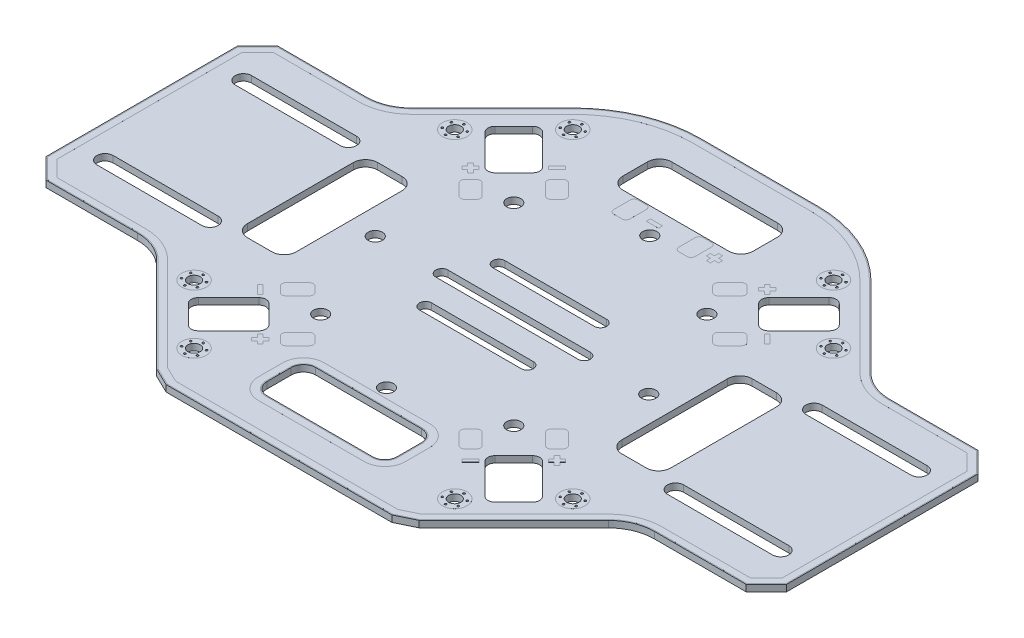
SolidWorks part; units mm, degrees
material "PLA"
ref_plane "Front Plane" through (0, 0, 0) normal (0, 0, 1) x (1, 0, 0)
ref_plane "Top Plane" through (0, 0, 0) normal (0, 1, 0) x (1, 0, 0)
ref_plane "Right Plane" through (0, 0, 0) normal (1, 0, 0) x (0, 0, -1)
sketch "Sketch1" plane through (0, 0, 0) normal (0, 1, 0) x (1, 0, 0)
  line L0 (0, 60.3186) -> (0, -57.6814) construction
  line L1 (-27.75, -57.6814) -> (27.75, -57.6814)
  line L2 (-13, -47.6814) -> (13, -47.6814)
  line L3 (-16, -38.6814) -> (-16, -44.6814)
  line L4 (16, -38.6814) -> (16, -44.6814)
  line L5 (-16, -41.6814) -> (16, -41.6814) construction
  line L6 (-13, -35.6814) -> (13, -35.6814)
  line L7 (-27.75, -57.6814) -> (-32.25, -55.502)
  line L8 (27.75, -57.6814) -> (32.25, -55.502)
  line L9 (-32.25, -55.502) -> (32.25, -55.502) construction
  line L10 (32.25, -55.502) -> (55.502, -32.25)
  line L11 (-32.25, -55.502) -> (-55.502, -32.25)
  line L12 (-43.876, 43.876) -> (43.876, -43.876) construction
  line L13 (-43.876, -43.876) -> (43.876, 43.876) construction
  line L14 (37.6888, -42.285) -> (42.285, -37.6888)
  line L15 (27.7893, -34.8604) -> (35.2139, -42.285)
  line L16 (34.8604, -27.7893) -> (42.285, -35.2139)
  line L17 (31.5016, -38.5727) -> (38.5727, -31.5016) construction
  line L18 (27.7893, -32.3855) -> (32.3855, -27.7893)
  line L19 (-38.5727, -31.5016) -> (-31.5016, -38.5727) construction
  line L20 (-35.2139, -42.285) -> (-27.7893, -34.8604)
  line L21 (-42.285, -35.2139) -> (-34.8604, -27.7893)
  line L22 (-32.3855, -27.7893) -> (-27.7893, -32.3855)
  line L23 (-42.285, -37.6888) -> (-37.6888, -42.285)
  line L24 (-63.5, -28.9371) -> (63.5, -28.9371) construction
  line L25 (63.5, -28.9371) -> (86, -28.9371)
  line L26 (-63.5, -28.9371) -> (-86, -28.9371)
  line L27 (-91, -23.9371) -> (-91, 23.0629)
  line L28 (91, -23.9371) -> (91, 23.0629)
  line L29 (-86, -28.9371) -> (-86, 28.0629) construction
  line L30 (86, -28.9371) -> (86, 28.0629) construction
  line L31 (-91, -0.4371) -> (-86, -0.4371) construction
  line L32 (86, -0.4371) -> (91, -0.4371) construction
  line L33 (86, -28.9371) -> (91, -23.9371)
  line L34 (-91, -23.9371) -> (-86, -28.9371)
  line L35 (91, 23.0629) -> (86, 28.0629)
  line L36 (-91, 23.0629) -> (-86, 28.0629)
  line L37 (-56.4271, 31.3248) -> (-36.6281, 51.1238)
  line L38 (36.6281, 51.1238) -> (56.4271, 31.3248)
  line L39 (-35.2139, 42.285) -> (-27.7893, 34.8604)
  line L40 (-36.6281, 51.1238) -> (-27.7893, 42.285) construction
  line L41 (-27.7893, 42.285) -> (-31.5016, 38.5727) construction
  line L42 (-42.285, 35.2139) -> (-34.8604, 27.7893)
  line L43 (-31.5016, 38.5727) -> (-38.5727, 31.5016) construction
  line L44 (-42.285, 37.6888) -> (-37.6888, 42.285)
  line L45 (-32.3855, 27.7893) -> (-27.7893, 32.3855)
  line L46 (-86, 28.0629) -> (-64.3021, 28.0629)
  line L47 (86, 28.0629) -> (64.3021, 28.0629)
  line L48 (37.6888, 42.285) -> (42.285, 37.6888)
  line L49 (27.7893, 32.3855) -> (32.3855, 27.7893)
  line L50 (27.7893, 34.8604) -> (35.2139, 42.285)
  line L51 (34.8604, 27.7893) -> (42.285, 35.2139)
  line L52 (31.5016, 38.5727) -> (38.5727, 31.5016) construction
  line L53 (31.5016, 38.5727) -> (27.7893, 42.285) construction
  line L54 (27.7893, 42.285) -> (36.6281, 51.1238) construction
  line L55 (-14.43, 60.3186) -> (14.43, 60.3186)
  line L56 (-13, 51.8186) -> (13, 51.8186)
  line L57 (-13, 39.8186) -> (13, 39.8186)
  line L58 (16, 48.8186) -> (16, 42.8186)
  line L59 (-16, 48.8186) -> (-16, 42.8186)
  line L60 (-12.5, -10.6814) -> (12.5, -10.6814)
  line L61 (-12.5, -7.6814) -> (12.5, -7.6814)
  line L62 (-17.5, -1.6814) -> (17.5, -1.6814)
  line L63 (-17.5, 1.3186) -> (17.5, 1.3186)
  line L64 (-12.5, 7.3186) -> (12.5, 7.3186)
  line L65 (-12.5, 10.3186) -> (12.5, 10.3186)
  line L66 (-52, 12.5629) -> (-52, -13.4371)
  line L67 (-86, -0.4371) -> (-52, -0.4371) construction
  line L68 (-40, 12.5629) -> (-40, -13.4371)
  line L69 (52, 12.5629) -> (52, -13.4371)
  line L70 (-49, 15.5629) -> (-43, 15.5629)
  line L71 (-49, -16.4371) -> (-43, -16.4371)
  line L72 (86, -0.4371) -> (52, -0.4371) construction
  line L73 (40, 12.5629) -> (40, -13.4371)
  line L74 (43, 15.5629) -> (49, 15.5629)
  line L75 (43, -16.4371) -> (49, -16.4371)
  line L76 (-83, 18.5629) -> (-57.2, 18.5629)
  line L77 (-83, 14.5629) -> (-57.2, 14.5629)
  line L78 (-83, -15.4371) -> (-57.2, -15.4371)
  line L79 (-83, -19.4371) -> (-57.2, -19.4371)
  line L80 (57.2, -15.4371) -> (83, -15.4371)
  line L81 (57.2, -19.4371) -> (83, -19.4371)
  line L82 (57.2, 18.5629) -> (83, 18.5629)
  line L83 (57.2, 14.5629) -> (83, 14.5629)
  line L84 (-46.5276, 32.0319) -> (-32.0319, 46.5276) construction
  line L85 (32.0319, -46.5276) -> (46.5276, -32.0319) construction
  arc A0 (-16, -44.6814) -> (-13, -47.6814) centre (-13, -44.6814) ccw
  arc A1 (-13, -35.6814) -> (-16, -38.6814) centre (-13, -38.6814) ccw
  arc A2 (16, -38.6814) -> (13, -35.6814) centre (13, -38.6814) ccw
  arc A3 (13, -47.6814) -> (16, -44.6814) centre (13, -44.6814) ccw
  arc A4 (27.7893, -32.3855) -> (27.7893, -34.8604) centre (29.0267, -33.6229) ccw
  arc A5 (34.8604, -27.7893) -> (32.3855, -27.7893) centre (33.6229, -29.0267) ccw
  arc A6 (35.2139, -42.285) -> (37.6888, -42.285) centre (36.4514, -41.0475) ccw
  arc A7 (42.285, -37.6888) -> (42.285, -35.2139) centre (41.0475, -36.4514) ccw
  arc A8 (-37.6888, -42.285) -> (-35.2139, -42.285) centre (-36.4514, -41.0475) ccw
  arc A9 (-42.285, -35.2139) -> (-42.285, -37.6888) centre (-41.0475, -36.4514) ccw
  arc A10 (-32.3855, -27.7893) -> (-34.8604, -27.7893) centre (-33.6229, -29.0267) ccw
  arc A11 (-27.7893, -34.8604) -> (-27.7893, -32.3855) centre (-29.0267, -33.6229) ccw
  arc A12 (-55.502, -32.25) -> (-63.5, -28.9371) centre (-63.5, -40.248) ccw
  arc A13 (63.5, -28.9371) -> (55.502, -32.25) centre (63.5, -40.248) ccw
  arc A14 (-42.285, 37.6888) -> (-42.285, 35.2139) centre (-41.0475, 36.4514) ccw
  arc A15 (-35.2139, 42.285) -> (-37.6888, 42.285) centre (-36.4514, 41.0475) ccw
  arc A16 (-27.7893, 32.3855) -> (-27.7893, 34.8604) centre (-29.0267, 33.6229) ccw
  arc A17 (-34.8604, 27.7893) -> (-32.3855, 27.7893) centre (-33.6229, 29.0267) ccw
  arc A18 (-64.3021, 28.0629) -> (-56.4271, 31.3248) centre (-64.3021, 39.1998) ccw
  arc A19 (56.4271, 31.3248) -> (64.3021, 28.0629) centre (64.3021, 39.1998) ccw
  arc A20 (27.7893, 34.8604) -> (27.7893, 32.3855) centre (29.0267, 33.6229) ccw
  arc A21 (37.6888, 42.285) -> (35.2139, 42.285) centre (36.4514, 41.0475) ccw
  arc A22 (42.285, 35.2139) -> (42.285, 37.6888) centre (41.0475, 36.4514) ccw
  arc A23 (32.3855, 27.7893) -> (34.8604, 27.7893) centre (33.6229, 29.0267) ccw
  arc A24 (-14.43, 60.3186) -> (-36.6281, 51.1238) centre (-14.43, 28.9257) ccw
  arc A25 (13, 39.8186) -> (16, 42.8186) centre (13, 42.8186) ccw
  arc A26 (36.6281, 51.1238) -> (14.43, 60.3186) centre (14.43, 28.9257) ccw
  arc A27 (16, 48.8186) -> (13, 51.8186) centre (13, 48.8186) ccw
  arc A28 (-16, 42.8186) -> (-13, 39.8186) centre (-13, 42.8186) ccw
  arc A29 (-13, 51.8186) -> (-16, 48.8186) centre (-13, 48.8186) ccw
  arc A30 (-12.5, -7.6814) -> (-12.5, -10.6814) centre (-12.5, -9.1814) ccw
  arc A31 (12.5, -10.6814) -> (12.5, -7.6814) centre (12.5, -9.1814) ccw
  arc A32 (-17.5, 1.3186) -> (-17.5, -1.6814) centre (-17.5, -0.1814) ccw
  arc A33 (17.5, -1.6814) -> (17.5, 1.3186) centre (17.5, -0.1814) ccw
  arc A34 (-12.5, 10.3186) -> (-12.5, 7.3186) centre (-12.5, 8.8186) ccw
  arc A35 (12.5, 7.3186) -> (12.5, 10.3186) centre (12.5, 8.8186) ccw
  arc A36 (-49, 15.5629) -> (-52, 12.5629) centre (-49, 12.5629) ccw
  arc A37 (-40, 12.5629) -> (-43, 15.5629) centre (-43, 12.5629) ccw
  arc A38 (-52, -13.4371) -> (-49, -16.4371) centre (-49, -13.4371) ccw
  arc A39 (-43, -16.4371) -> (-40, -13.4371) centre (-43, -13.4371) ccw
  arc A40 (43, 15.5629) -> (40, 12.5629) centre (43, 12.5629) ccw
  arc A41 (52, 12.5629) -> (49, 15.5629) centre (49, 12.5629) ccw
  arc A42 (40, -13.4371) -> (43, -16.4371) centre (43, -13.4371) ccw
  arc A43 (49, -16.4371) -> (52, -13.4371) centre (49, -13.4371) ccw
  arc A44 (-57.2, 14.5629) -> (-57.2, 18.5629) centre (-57.2, 16.5629) ccw
  arc A45 (-83, 18.5629) -> (-83, 14.5629) centre (-83, 16.5629) ccw
  arc A46 (-83, -15.4371) -> (-83, -19.4371) centre (-83, -17.4371) ccw
  arc A47 (-57.2, -19.4371) -> (-57.2, -15.4371) centre (-57.2, -17.4371) ccw
  arc A48 (57.2, -15.4371) -> (57.2, -19.4371) centre (57.2, -17.4371) ccw
  arc A49 (83, -19.4371) -> (83, -15.4371) centre (83, -17.4371) ccw
  arc A50 (57.2, 18.5629) -> (57.2, 14.5629) centre (57.2, 16.5629) ccw
  arc A51 (83, 14.5629) -> (83, 18.5629) centre (83, 16.5629) ccw
  circle A52 centre (-32.0319, 46.5276) radius 1.5
  circle A53 centre (-46.5276, 32.0319) radius 1.5
  circle A54 centre (32.0319, -46.5276) radius 1.5
  circle A55 centre (46.5276, -32.0319) radius 1.5
  circle A56 centre (-46.5276, -32.0319) radius 1.5
  circle A57 centre (-32.0319, -46.5276) radius 1.5
  circle A58 centre (32.0319, 46.5276) radius 1.5
  circle A59 centre (46.5276, 32.0319) radius 1.5
  point P4 (-35.0371, 35.0371)
  point P5 (0, -47.6814)
  point P14 (0, -41.6814)
  point P15 (0, -35.6814)
  point P19 (0, -55.502)
  point P29 (0, 0)
  point P30 (39.9869, -39.9869)
  point P32 (0, 0)
  point P42 (30.0874, -30.0874)
  point P43 (35.0371, -35.0371)
  point P50 (-35.0371, -35.0371)
  point P53 (-38.5727, -31.5016)
  point P62 (-39.9869, -39.9869)
  point P63 (-30.0874, -30.0874)
  point P70 (0, -28.9371)
  point P99 (-39.9869, 39.9869)
  point P102 (-30.0874, 30.0874)
  point P119 (35.0371, 35.0371)
  point P122 (39.9869, 39.9869)
  point P123 (30.0874, 30.0874)
  point P135 (0, 51.8186)
  point P138 (0, 39.8186)
  point P147 (0, -10.6814)
  point P151 (-14, -9.1814)
  point P153 (14, -9.1814)
  point P156 (0, -1.6814)
  point P158 (-19, -0.1814)
  point P162 (19, -0.1814)
  point P167 (0, 7.3186)
  point P203 (-85, 16.5629)
  point P205 (-55.2, 16.5629)
  point P217 (85, -17.4371)
  point P229 (-39.2798, 39.2798)
  point P232 (39.2798, -39.2798)
  dimension "D5" = 12
  dimension "D6" = 55.5
  dimension "D14" = 14
  dimension "D15" = 127
  dimension "D16" = 22.5
  dimension "D23" = 8.5
  dimension "D24" = 25
  dimension "D25" = 3
  dimension "D28" = 3
  dimension "D31" = 39
  dimension "D32" = 9.5
  dimension "D34" = 29.8
  dimension "D38" = 6
  dimension "D39" = 3
  dimension "D1" = 118
  dimension "D2" = 10
  dimension "D3" = 32
  dimension "D4" = 6
  dimension "D7" = 64.5
  dimension "D8" = 5
  dimension "D9" = 124.1
  dimension "D10" = 45
  dimension "D11" = 5.5
  dimension "D12" = 6.5
  dimension "D13" = 10
  dimension "D17" = 22.5
  dimension "D18" = 5
  dimension "D19" = 45
  dimension "D20" = 47
  dimension "D21" = 28
  dimension "D22" = 5.25
  dimension "D26" = 28
  dimension "D27" = 6
  dimension "D29" = 38
  dimension "D30" = 6
  dimension "D33" = 4
  dimension "D35" = 6
  dimension "D36" = 9.5
  dimension "D37" = 4
  dimension "D40" = 6.5
  dimension "D41" = 6.5
extrude "Boss-Extrude1" add sketch "Sketch1" along normal blind 0.8 and the other way blind 0.8
sketch "Sketch2" plane through (0, 0.8, 0) normal (0, 1, 0) x (1, 0, 0)
  line L0 (-27.6926, -57.4314) -> (27.6926, -57.4314)
  line L1 (-27.75, -57.6814) -> (27.75, -57.6814) construction
  line L2 (-27.6926, -57.4314) -> (-32.1031, -55.2953)
  line L3 (-32.25, -55.502) -> (-27.75, -57.6814) construction
  line L4 (27.6926, -57.4314) -> (32.1031, -55.2953)
  line L5 (27.75, -57.6814) -> (32.25, -55.502) construction
  line L6 (0, -57.6814) -> (0, -57.4314) construction
  line L7 (-32.1031, -55.2953) -> (-55.3252, -32.0732)
  line L8 (-55.502, -32.25) -> (-32.25, -55.502) construction
  line L9 (32.1031, -55.2953) -> (55.3252, -32.0732)
  line L10 (32.25, -55.502) -> (55.502, -32.25) construction
  line L11 (-85.8964, -28.6871) -> (-63.5, -28.6871)
  line L12 (-85.8964, -28.6871) -> (-90.75, -23.8335)
  line L13 (-91, -23.9371) -> (-86, -28.9371) construction
  line L14 (-86, -28.9371) -> (-63.5, -28.9371) construction
  line L15 (63.5, -28.6871) -> (85.8964, -28.6871)
  line L16 (85.8964, -28.6871) -> (90.75, -23.8335)
  line L17 (-90.75, -23.8335) -> (-90.75, 22.9593)
  line L18 (-91, 23.0629) -> (-91, -23.9371) construction
  line L19 (-90.75, 22.9593) -> (-85.8964, 27.8129)
  line L20 (-85.8964, 27.8129) -> (-64.3021, 27.8129)
  line L21 (-64.3021, 28.0629) -> (-86, 28.0629) construction
  line L22 (-56.2503, 31.1481) -> (-36.4514, 50.947)
  line L23 (-36.6281, 51.1238) -> (-56.4271, 31.3248) construction
  line L24 (-14.43, 60.0686) -> (14.43, 60.0686)
  line L25 (14.43, 60.3186) -> (-14.43, 60.3186) construction
  line L26 (56.2503, 31.1481) -> (36.4514, 50.947)
  line L27 (56.4271, 31.3248) -> (36.6281, 51.1238) construction
  line L28 (64.3021, 27.8129) -> (85.8964, 27.8129)
  line L29 (86, 28.0629) -> (64.3021, 28.0629) construction
  line L30 (85.8964, 27.8129) -> (90.75, 22.9593)
  line L31 (91, 23.0629) -> (86, 28.0629) construction
  line L32 (90.75, 22.9593) -> (90.75, -23.8335)
  line L33 (-55.0836, 29.9813) -> (-35.2846, 49.7803)
  line L34 (-14.43, 58.4186) -> (14.43, 58.4186)
  line L35 (55.0836, 29.9813) -> (35.2846, 49.7803)
  line L36 (64.3021, 26.1629) -> (85.213, 26.1629)
  line L37 (85.213, 26.1629) -> (89.1, 22.2759)
  line L38 (89.1, 22.2759) -> (89.1, -23.1501)
  line L39 (85.213, -27.0371) -> (89.1, -23.1501)
  line L40 (63.5, -27.0371) -> (85.213, -27.0371)
  line L41 (31.1332, -53.9317) -> (54.1584, -30.9065)
  line L42 (27.3141, -55.7814) -> (31.1332, -53.9317)
  line L43 (-27.3141, -55.7814) -> (27.3141, -55.7814)
  line L44 (-27.3141, -55.7814) -> (-31.1332, -53.9317)
  line L45 (-31.1332, -53.9317) -> (-54.1584, -30.9065)
  line L46 (-85.213, -27.0371) -> (-63.5, -27.0371)
  line L47 (-85.213, -27.0371) -> (-89.1, -23.1501)
  line L48 (-89.1, -23.1501) -> (-89.1, 22.2759)
  line L49 (-89.1, 22.2759) -> (-85.213, 26.1629)
  line L50 (-85.213, 26.1629) -> (-64.3021, 26.1629)
  line L51 (-13, -35.4314) -> (13, -35.4314)
  line L52 (-16.25, -38.6814) -> (-16.25, -44.6814)
  line L53 (-13, -47.9314) -> (13, -47.9314)
  line L54 (16.25, -44.6814) -> (16.25, -38.6814)
  line L55 (16, -44.6814) -> (16, -38.6814) construction
  line L56 (13, -35.6814) -> (-13, -35.6814) construction
  line L57 (-16, -38.6814) -> (-16, -44.6814) construction
  line L58 (-13, -47.6814) -> (13, -47.6814) construction
  line L59 (-13, -33.6314) -> (13, -33.6314)
  line L60 (18.05, -44.6814) -> (18.05, -38.6814)
  line L61 (-13, -49.7314) -> (13, -49.7314)
  line L62 (-18.05, -38.6814) -> (-18.05, -44.6814)
  line L63 (32.0319, -43.5276) -> (32.0319, -44.2776) construction
  line L64 (-32.0319, -44.2776) -> (-33.9805, -45.4026) construction
  line L65 (-33.9805, -45.4026) -> (-33.9805, -47.6526) construction
  line L66 (-33.9805, -47.6526) -> (-32.0319, -48.7776) construction
  line L67 (-32.0319, -48.7776) -> (-30.0834, -47.6526) construction
  line L68 (-30.0834, -47.6526) -> (-30.0834, -45.4026) construction
  line L69 (-30.0834, -45.4026) -> (-32.0319, -44.2776) construction
  line L70 (-46.5276, -29.7819) -> (-48.4762, -30.9069) construction
  line L71 (-48.4762, -30.9069) -> (-48.4762, -33.1569) construction
  line L72 (-48.4762, -33.1569) -> (-46.5276, -34.2819) construction
  line L73 (-46.5276, -34.2819) -> (-44.5791, -33.1569) construction
  line L74 (-44.5791, -33.1569) -> (-44.5791, -30.9069) construction
  line L75 (-44.5791, -30.9069) -> (-46.5276, -29.7819) construction
  line L76 (-46.5276, 34.2819) -> (-48.4762, 33.1569) construction
  line L77 (-48.4762, 33.1569) -> (-48.4762, 30.9069) construction
  line L78 (-48.4762, 30.9069) -> (-46.5276, 29.7819) construction
  line L79 (-46.5276, 29.7819) -> (-44.5791, 30.9069) construction
  line L80 (-44.5791, 30.9069) -> (-44.5791, 33.1569) construction
  line L81 (-44.5791, 33.1569) -> (-46.5276, 34.2819) construction
  line L82 (-32.0319, 48.7776) -> (-33.9805, 47.6526) construction
  line L83 (-33.9805, 47.6526) -> (-33.9805, 45.4026) construction
  line L84 (-33.9805, 45.4026) -> (-32.0319, 44.2776) construction
  line L85 (-32.0319, 44.2776) -> (-30.0834, 45.4026) construction
  line L86 (-30.0834, 45.4026) -> (-30.0834, 47.6526) construction
  line L87 (-30.0834, 47.6526) -> (-32.0319, 48.7776) construction
  line L88 (32.0319, 48.7776) -> (30.0834, 47.6526) construction
  line L89 (30.0834, 47.6526) -> (30.0834, 45.4026) construction
  line L90 (30.0834, 45.4026) -> (32.0319, 44.2776) construction
  line L91 (32.0319, 44.2776) -> (33.9805, 45.4026) construction
  line L92 (33.9805, 45.4026) -> (33.9805, 47.6526) construction
  line L93 (33.9805, 47.6526) -> (32.0319, 48.7776) construction
  line L94 (46.5276, 34.2819) -> (44.5791, 33.1569) construction
  line L95 (44.5791, 33.1569) -> (44.5791, 30.9069) construction
  line L96 (44.5791, 30.9069) -> (46.5276, 29.7819) construction
  line L97 (46.5276, 29.7819) -> (48.4762, 30.9069) construction
  line L98 (48.4762, 30.9069) -> (48.4762, 33.1569) construction
  line L99 (48.4762, 33.1569) -> (46.5276, 34.2819) construction
  line L100 (46.5276, -29.7819) -> (44.5791, -30.9069) construction
  line L101 (44.5791, -30.9069) -> (44.5791, -33.1569) construction
  line L102 (44.5791, -33.1569) -> (46.5276, -34.2819) construction
  line L103 (46.5276, -34.2819) -> (48.4762, -33.1569) construction
  line L104 (48.4762, -33.1569) -> (48.4762, -30.9069) construction
  line L105 (48.4762, -30.9069) -> (46.5276, -29.7819) construction
  line L106 (32.0319, -44.2776) -> (30.0834, -45.4026) construction
  line L107 (30.0834, -45.4026) -> (30.0834, -47.6526) construction
  line L108 (30.0834, -47.6526) -> (32.0319, -48.7776) construction
  line L109 (32.0319, -48.7776) -> (33.9805, -47.6526) construction
  line L110 (33.9805, -47.6526) -> (33.9805, -45.4026) construction
  line L111 (33.9805, -45.4026) -> (32.0319, -44.2776) construction
  line L112 (32.0319, -44.2776) -> (32.0319, -45.0276) construction
  arc A0 (-55.3252, -32.0732) -> (-63.5, -28.6871) centre (-63.5, -40.248) ccw
  arc A1 (-55.502, -32.25) -> (-63.5, -28.9371) centre (-63.5, -40.248) ccw construction
  arc A2 (63.5, -28.6871) -> (55.3252, -32.0732) centre (63.5, -40.248) ccw
  arc A3 (63.5, -28.9371) -> (55.502, -32.25) centre (63.5, -40.248) ccw construction
  arc A4 (-64.3021, 27.8129) -> (-56.2503, 31.1481) centre (-64.3021, 39.1998) ccw
  arc A5 (-64.3021, 28.0629) -> (-56.4271, 31.3248) centre (-64.3021, 39.1998) ccw construction
  arc A6 (-14.43, 60.0686) -> (-36.4514, 50.947) centre (-14.43, 28.9257) ccw
  arc A7 (-14.43, 60.3186) -> (-36.6281, 51.1238) centre (-14.43, 28.9257) ccw construction
  arc A8 (36.4514, 50.947) -> (14.43, 60.0686) centre (14.43, 28.9257) ccw
  arc A9 (36.6281, 51.1238) -> (14.43, 60.3186) centre (14.43, 28.9257) ccw construction
  arc A10 (56.2503, 31.1481) -> (64.3021, 27.8129) centre (64.3021, 39.1998) ccw
  arc A11 (56.4271, 31.3248) -> (64.3021, 28.0629) centre (64.3021, 39.1998) ccw construction
  arc A12 (-14.43, 58.4186) -> (-35.2846, 49.7803) centre (-14.43, 28.9257) ccw
  arc A13 (35.2846, 49.7803) -> (14.43, 58.4186) centre (14.43, 28.9257) ccw
  arc A14 (55.0836, 29.9813) -> (64.3021, 26.1629) centre (64.3021, 39.1998) ccw
  arc A15 (63.5, -27.0371) -> (54.1584, -30.9065) centre (63.5, -40.248) ccw
  arc A16 (-54.1584, -30.9065) -> (-63.5, -27.0371) centre (-63.5, -40.248) ccw
  arc A17 (-64.3021, 26.1629) -> (-55.0836, 29.9813) centre (-64.3021, 39.1998) ccw
  arc A18 (-13, -35.4314) -> (-16.25, -38.6814) centre (-13, -38.6814) ccw
  arc A19 (16.25, -38.6814) -> (13, -35.4314) centre (13, -38.6814) ccw
  arc A20 (-16.25, -44.6814) -> (-13, -47.9314) centre (-13, -44.6814) ccw
  arc A21 (13, -47.9314) -> (16.25, -44.6814) centre (13, -44.6814) ccw
  arc A22 (-13, -35.6814) -> (-16, -38.6814) centre (-13, -38.6814) ccw construction
  arc A23 (-16, -44.6814) -> (-13, -47.6814) centre (-13, -44.6814) ccw construction
  arc A24 (16, -38.6814) -> (13, -35.6814) centre (13, -38.6814) ccw construction
  arc A25 (13, -47.6814) -> (16, -44.6814) centre (13, -44.6814) ccw construction
  arc A26 (18.05, -38.6814) -> (13, -33.6314) centre (13, -38.6814) ccw
  arc A27 (13, -49.7314) -> (18.05, -44.6814) centre (13, -44.6814) ccw
  arc A28 (-18.05, -44.6814) -> (-13, -49.7314) centre (-13, -44.6814) ccw
  arc A29 (-13, -33.6314) -> (-18.05, -38.6814) centre (-13, -38.6814) ccw
  circle A30 centre (-32.0319, -46.5276) radius 1.5
  circle A31 centre (-46.5276, -32.0319) radius 1.5
  circle A32 centre (-46.5276, 32.0319) radius 1.5
  circle A33 centre (-32.0319, 46.5276) radius 1.5
  circle A34 centre (32.0319, 46.5276) radius 1.5
  circle A35 centre (46.5276, 32.0319) radius 1.5
  circle A36 centre (46.5276, -32.0319) radius 1.5
  circle A37 centre (32.0319, -46.5276) radius 1.5
  circle A38 centre (-32.0319, -46.5276) radius 1.5 construction
  circle A39 centre (-46.5276, -32.0319) radius 1.5 construction
  circle A40 centre (-46.5276, 32.0319) radius 1.5 construction
  circle A41 centre (-32.0319, 46.5276) radius 1.5 construction
  circle A42 centre (32.0319, 46.5276) radius 1.5 construction
  circle A43 centre (46.5276, 32.0319) radius 1.5 construction
  circle A44 centre (46.5276, -32.0319) radius 1.5 construction
  circle A45 centre (32.0319, -46.5276) radius 1.5 construction
  circle A46 centre (-32.0319, -46.5276) radius 3
  circle A47 centre (-46.5276, -32.0319) radius 3
  circle A48 centre (-46.5276, 32.0319) radius 3
  circle A49 centre (-32.0319, 46.5276) radius 3
  circle A50 centre (32.0319, 46.5276) radius 3
  circle A51 centre (46.5276, 32.0319) radius 3
  circle A52 centre (46.5276, -32.0319) radius 3
  circle A53 centre (32.0319, -46.5276) radius 3
  circle A54 centre (-32.0319, -46.5276) radius 1.9486 construction
  circle A55 centre (-46.5276, -32.0319) radius 1.9486 construction
  circle A56 centre (-46.5276, 32.0319) radius 1.9486 construction
  circle A57 centre (-32.0319, 46.5276) radius 1.9486 construction
  circle A58 centre (32.0319, 46.5276) radius 1.9486 construction
  circle A59 centre (46.5276, 32.0319) radius 1.9486 construction
  circle A60 centre (46.5276, -32.0319) radius 1.9486 construction
  circle A61 centre (32.0319, -46.5276) radius 1.9486 construction
  circle A62 centre (32.0319, -44.2776) radius 0.25
  circle A63 centre (33.9805, -45.4026) radius 0.25
  circle A64 centre (33.9805, -47.6526) radius 0.25
  circle A65 centre (32.0319, -48.7776) radius 0.25
  circle A66 centre (30.0834, -47.6526) radius 0.25
  circle A67 centre (30.0834, -45.4026) radius 0.25
  circle A68 centre (46.5276, -34.2819) radius 0.25
  circle A69 centre (48.4762, -33.1569) radius 0.25
  circle A70 centre (48.4762, -30.9069) radius 0.25
  circle A71 centre (46.5276, -29.7819) radius 0.25
  circle A72 centre (44.5791, -30.9069) radius 0.25
  circle A73 centre (44.5791, -33.1569) radius 0.25
  circle A74 centre (46.5276, 29.7819) radius 0.25
  circle A75 centre (48.4762, 30.9069) radius 0.25
  circle A76 centre (48.4762, 33.1569) radius 0.25
  circle A77 centre (46.5276, 34.2819) radius 0.25
  circle A78 centre (44.5791, 33.1569) radius 0.25
  circle A79 centre (44.5791, 30.9069) radius 0.25
  circle A80 centre (32.0319, 44.2776) radius 0.25
  circle A81 centre (33.9805, 45.4026) radius 0.25
  circle A82 centre (33.9805, 47.6526) radius 0.25
  circle A83 centre (32.0319, 48.7776) radius 0.25
  circle A84 centre (30.0834, 47.6526) radius 0.25
  circle A85 centre (30.0834, 45.4026) radius 0.25
  circle A86 centre (-32.0319, 48.7776) radius 0.25
  circle A87 centre (-30.0834, 47.6526) radius 0.25
  circle A88 centre (-30.0834, 45.4026) radius 0.25
  circle A89 centre (-32.0319, 44.2776) radius 0.25
  circle A90 centre (-33.9805, 47.6526) radius 0.25
  circle A91 centre (-33.9805, 45.4026) radius 0.25
  circle A92 centre (-46.5276, 29.7819) radius 0.25
  circle A93 centre (-44.5791, 30.9069) radius 0.25
  circle A94 centre (-44.5791, 33.1569) radius 0.25
  circle A95 centre (-46.5276, 34.2819) radius 0.25
  circle A96 centre (-48.4762, 33.1569) radius 0.25
  circle A97 centre (-48.4762, 30.9069) radius 0.25
  circle A98 centre (-46.5276, -29.7819) radius 0.25
  circle A99 centre (-44.5791, -30.9069) radius 0.25
  circle A100 centre (-44.5791, -33.1569) radius 0.25
  circle A101 centre (-46.5276, -34.2819) radius 0.25
  circle A102 centre (-48.4762, -33.1569) radius 0.25
  circle A103 centre (-48.4762, -30.9069) radius 0.25
  circle A104 centre (-32.0319, -44.2776) radius 0.25
  circle A105 centre (-30.0834, -45.4026) radius 0.25
  circle A106 centre (-30.0834, -47.6526) radius 0.25
  circle A107 centre (-32.0319, -48.7776) radius 0.25
  circle A108 centre (-33.9805, -47.6526) radius 0.25
  circle A109 centre (-33.9805, -45.4026) radius 0.25
  dimension "D2" = 0.25
  dimension "D5" = 0.25
  dimension "D7" = 1.65
  dimension "D8" = 0.25
  dimension "D10" = 6
  dimension "D11" = 0.5
  dimension "D1" = 0.25
  dimension "D3" = 0.25
  dimension "D4" = 0.25
  dimension "D6" = 0.25
  dimension "D9" = 1.8
extrude "Boss-Extrude2" add sketch "Sketch2" along normal blind 0.001 contours A10 L26 A8 L24 A6 L22 A4 L20 L19 L17 L12 L11 A0 L7 L2 L0 L4 L9 A2 L15 L16 L32 L30 L28 L50 A17 L33 A12 L34 A13 L35 A14 L36 L37 L38 L39 L40 A15 L41 L42 L43 L44 L45 A16 L46 L47 L48 L49 | A46 A109 A108 A107 A106 A105 A104 A30 | A47 A103 A102 A101 A100 A99 A98 A31 | A48 A97 A96 A95 A94 A93 A92 A32 | A49 A91 A90 A89 A88 A87 A86 A33 | A50 A85 A84 A83 A82 A81 A80 A34 | A51 A79 A78 A77 A76 A75 A74 A35 | A52 A73 A72 A71 A70 A69 A68 A36 | A53 A67 A66 A65 A64 A63 A62 A37 | L59 A29 L62 A28 L61 A27 L60 A26 A21 L53 A20 L52 A18 L51 A19 L54 region at (-29.8036, 0.8, 56.1688) region at (0, 0.8, 34.0267) region at (-34.9471, 0.8, 46.5276) region at (-49.4428, 0.8, 32.0319) region at (-49.4428, 0.8, -32.0319) region at (-34.9471, 0.8, -46.5276) region at (29.1168, 0.8, -46.5276) region at (43.6125, 0.8, -32.0319) region at (43.6125, 0.8, 32.0319) region at (29.1168, 0.8, 46.5276)
mirror "Mirror1" about plane through (0, 0, 0) normal (0, 1, 0) of "Boss-Extrude2"
sketch "Sketch5" plane through (0, 0.8, 0) normal (0, 1, 0) x (1, 0, 0)
  line L0 (35.7442, -27.259) -> (36.4514, -26.5519)
  line L1 (35.0371, -26.5519) -> (35.7442, -25.8448)
  line L2 (35.3907, -26.9054) -> (37.512, -24.7841) construction
  line L3 (35.0371, -26.5519) -> (35.7442, -27.259)
  line L4 (37.1585, -24.4305) -> (37.8656, -25.1376)
  line L5 (42.285, -35.2139) -> (34.8604, -27.7893) construction
  line L6 (32.1031, -55.2953) -> (55.3252, -32.0732) construction
  line L8 (35.3907, -24.7841) -> (37.512, -26.9054) construction
  line L9 (35.0371, -25.1376) -> (35.7442, -24.4305)
  line L10 (37.1585, -27.259) -> (37.8656, -26.5519)
  line L11 (35.0371, -25.1376) -> (35.7442, -25.8448)
  line L12 (35.7442, -24.4305) -> (36.4514, -25.1376)
  line L13 (36.4514, -26.5519) -> (37.1585, -27.259)
  line L14 (36.4514, -25.1376) -> (37.1585, -24.4305)
  line L15 (37.1585, -25.8448) -> (37.8656, -26.5519)
  line L16 (37.1585, -25.8448) -> (37.8656, -25.1376)
  line L17 (26.9054, -35.3907) -> (24.7841, -37.512) construction
  line L18 (26.5519, -35.0371) -> (27.259, -35.7442)
  line L19 (27.7893, -34.8604) -> (35.2139, -42.285) construction
  line L20 (24.4305, -37.1585) -> (25.1376, -37.8656)
  line L21 (24.4305, -37.1585) -> (26.5519, -35.0371)
  line L22 (25.1376, -37.8656) -> (27.259, -35.7442)
  line L23 (-37.1585, -24.4305) -> (-37.8656, -25.1376)
  line L24 (-37.1585, -24.4305) -> (-35.0371, -26.5519)
  line L25 (-37.8656, -25.1376) -> (-35.7442, -27.259)
  line L26 (-35.3907, -26.9054) -> (-37.512, -24.7841) construction
  line L27 (-35.0371, -26.5519) -> (-35.7442, -27.259)
  line L28 (-26.5519, -35.0371) -> (-27.259, -35.7442)
  line L29 (-27.259, -35.7442) -> (-26.5519, -36.4514)
  line L30 (-26.5519, -36.4514) -> (-27.259, -37.1585)
  line L31 (-27.259, -37.1585) -> (-26.5519, -37.8656)
  line L32 (-25.8448, -37.1585) -> (-26.5519, -37.8656)
  line L33 (-25.8448, -37.1585) -> (-25.1376, -37.8656)
  line L34 (-24.4305, -37.1585) -> (-25.1376, -37.8656)
  line L35 (-25.1376, -36.4514) -> (-24.4305, -37.1585)
  line L36 (-24.4305, -35.7442) -> (-25.1376, -36.4514)
  line L37 (-25.1376, -35.0371) -> (-24.4305, -35.7442)
  line L38 (-25.1376, -35.0371) -> (-25.8448, -35.7442)
  line L39 (-26.5519, -35.0371) -> (-25.8448, -35.7442)
  line L40 (-26.9054, -35.3907) -> (-24.7841, -37.512) construction
  line L41 (-24.7841, -35.3907) -> (-26.9054, -37.512) construction
  line L42 (-24.4305, 37.1585) -> (-25.1376, 37.8656)
  line L43 (-24.4305, 37.1585) -> (-26.5519, 35.0371)
  line L44 (-25.1376, 37.8656) -> (-27.259, 35.7442)
  line L45 (-26.9054, 35.3907) -> (-24.7841, 37.512) construction
  line L46 (-26.5519, 35.0371) -> (-27.259, 35.7442)
  line L47 (-35.0371, 26.5519) -> (-35.7442, 27.259)
  line L48 (-35.7442, 27.259) -> (-36.4514, 26.5519)
  line L49 (-36.4514, 26.5519) -> (-37.1585, 27.259)
  line L50 (-37.1585, 27.259) -> (-37.8656, 26.5519)
  line L51 (-37.1585, 25.8448) -> (-37.8656, 26.5519)
  line L52 (-37.1585, 25.8448) -> (-37.8656, 25.1376)
  line L53 (-37.1585, 24.4305) -> (-37.8656, 25.1376)
  line L54 (-36.4514, 25.1376) -> (-37.1585, 24.4305)
  line L55 (-35.7442, 24.4305) -> (-36.4514, 25.1376)
  line L56 (-35.0371, 25.1376) -> (-35.7442, 24.4305)
  line L57 (-35.0371, 25.1376) -> (-35.7442, 25.8448)
  line L58 (-35.0371, 26.5519) -> (-35.7442, 25.8448)
  line L59 (-35.3907, 26.9054) -> (-37.512, 24.7841) construction
  line L60 (-35.3907, 24.7841) -> (-37.512, 26.9054) construction
  line L61 (37.1585, 24.4305) -> (37.8656, 25.1376)
  line L62 (37.1585, 24.4305) -> (35.0371, 26.5519)
  line L63 (37.8656, 25.1376) -> (35.7442, 27.259)
  line L64 (35.3907, 26.9054) -> (37.512, 24.7841) construction
  line L65 (35.0371, 26.5519) -> (35.7442, 27.259)
  line L66 (26.5519, 35.0371) -> (27.259, 35.7442)
  line L67 (27.259, 35.7442) -> (26.5519, 36.4514)
  line L68 (26.5519, 36.4514) -> (27.259, 37.1585)
  line L69 (27.259, 37.1585) -> (26.5519, 37.8656)
  line L70 (25.8448, 37.1585) -> (26.5519, 37.8656)
  line L71 (25.8448, 37.1585) -> (25.1376, 37.8656)
  line L72 (24.4305, 37.1585) -> (25.1376, 37.8656)
  line L73 (25.1376, 36.4514) -> (24.4305, 37.1585)
  line L74 (24.4305, 35.7442) -> (25.1376, 36.4514)
  line L75 (25.1376, 35.0371) -> (24.4305, 35.7442)
  line L76 (25.1376, 35.0371) -> (25.8448, 35.7442)
  line L77 (26.5519, 35.0371) -> (25.8448, 35.7442)
  line L78 (26.9054, 35.3907) -> (24.7841, 37.512) construction
  line L79 (24.7841, 35.3907) -> (26.9054, 37.512) construction
  line L80 (-36.6281, 51.1238) -> (-56.4271, 31.3248) construction
  line L81 (29.0267, -19.8343) -> (30.4409, -18.4201)
  line L82 (31.8552, -18.4201) -> (34.6836, -21.2486)
  line L83 (29.0267, -21.2486) -> (31.8552, -24.077)
  line L84 (33.2694, -24.077) -> (34.6836, -22.6628)
  line L85 (30.4409, -22.6628) -> (33.2694, -19.8343) construction
  line L86 (29.7338, -19.1272) -> (33.9765, -23.3699) construction
  line L87 (32.3855, -27.7893) -> (27.7893, -32.3855) construction
  line L88 (18.4201, -31.8552) -> (21.2486, -34.6836)
  line L89 (18.4201, -30.4409) -> (19.8343, -29.0267)
  line L90 (21.2486, -29.0267) -> (24.077, -31.8552)
  line L91 (22.6628, -34.6836) -> (24.077, -33.2694)
  line L92 (19.8343, -33.2694) -> (22.6628, -30.4409) construction
  line L93 (19.1272, -29.7338) -> (23.3699, -33.9765) construction
  line L94 (-34.6836, -22.6628) -> (-33.2694, -24.077)
  line L95 (-31.8552, -18.4201) -> (-34.6836, -21.2486)
  line L96 (-30.4409, -18.4201) -> (-29.0267, -19.8343)
  line L97 (-29.0267, -21.2486) -> (-31.8552, -24.077)
  line L98 (-29.7338, -19.1272) -> (-33.9765, -23.3699) construction
  line L99 (-33.2694, -19.8343) -> (-30.4409, -22.6628) construction
  line L100 (-21.2486, -29.0267) -> (-24.077, -31.8552)
  line L101 (-24.077, -33.2694) -> (-22.6628, -34.6836)
  line L102 (-18.4201, -31.8552) -> (-21.2486, -34.6836)
  line L103 (-19.8343, -29.0267) -> (-18.4201, -30.4409)
  line L104 (-19.1272, -29.7338) -> (-23.3699, -33.9765) construction
  line L105 (-22.6628, -30.4409) -> (-19.8343, -33.2694) construction
  line L106 (-22.6628, 34.6836) -> (-24.077, 33.2694)
  line L107 (-18.4201, 31.8552) -> (-21.2486, 34.6836)
  line L108 (-18.4201, 30.4409) -> (-19.8343, 29.0267)
  line L109 (-21.2486, 29.0267) -> (-24.077, 31.8552)
  line L110 (-19.1272, 29.7338) -> (-23.3699, 33.9765) construction
  line L111 (-19.8343, 33.2694) -> (-22.6628, 30.4409) construction
  line L112 (-29.0267, 21.2486) -> (-31.8552, 24.077)
  line L113 (-33.2694, 24.077) -> (-34.6836, 22.6628)
  line L114 (-31.8552, 18.4201) -> (-34.6836, 21.2486)
  line L115 (-29.0267, 19.8343) -> (-30.4409, 18.4201)
  line L116 (-29.7338, 19.1272) -> (-33.9765, 23.3699) construction
  line L117 (-30.4409, 22.6628) -> (-33.2694, 19.8343) construction
  line L118 (34.6836, 22.6628) -> (33.2694, 24.077)
  line L119 (31.8552, 18.4201) -> (34.6836, 21.2486)
  line L120 (30.4409, 18.4201) -> (29.0267, 19.8343)
  line L121 (29.0267, 21.2486) -> (31.8552, 24.077)
  line L122 (29.7338, 19.1272) -> (33.9765, 23.3699) construction
  line L123 (33.2694, 19.8343) -> (30.4409, 22.6628) construction
  line L124 (21.2486, 29.0267) -> (24.077, 31.8552)
  line L125 (24.077, 33.2694) -> (22.6628, 34.6836)
  line L126 (18.4201, 31.8552) -> (21.2486, 34.6836)
  line L127 (19.8343, 29.0267) -> (18.4201, 30.4409)
  line L128 (19.1272, 29.7338) -> (23.3699, 33.9765) construction
  line L129 (22.6628, 30.4409) -> (19.8343, 33.2694) construction
  line L130 (32.25, -55.502) -> (55.502, -32.25) construction
  arc A0 (31.8552, -18.4201) -> (30.4409, -18.4201) centre (31.1481, -19.1272) ccw
  arc A1 (29.0267, -19.8343) -> (29.0267, -21.2486) centre (29.7338, -20.5415) ccw
  arc A2 (31.8552, -24.077) -> (33.2694, -24.077) centre (32.5623, -23.3699) ccw
  arc A3 (34.6836, -22.6628) -> (34.6836, -21.2486) centre (33.9765, -21.9557) ccw
  arc A4 (18.4201, -30.4409) -> (18.4201, -31.8552) centre (19.1272, -31.1481) ccw
  arc A5 (21.2486, -29.0267) -> (19.8343, -29.0267) centre (20.5415, -29.7338) ccw
  arc A6 (24.077, -33.2694) -> (24.077, -31.8552) centre (23.3699, -32.5623) ccw
  arc A7 (21.2486, -34.6836) -> (22.6628, -34.6836) centre (21.9557, -33.9765) ccw
  arc A8 (-33.2694, -24.077) -> (-31.8552, -24.077) centre (-32.5623, -23.3699) ccw
  arc A9 (-34.6836, -21.2486) -> (-34.6836, -22.6628) centre (-33.9765, -21.9557) ccw
  arc A10 (-30.4409, -18.4201) -> (-31.8552, -18.4201) centre (-31.1481, -19.1272) ccw
  arc A11 (-29.0267, -21.2486) -> (-29.0267, -19.8343) centre (-29.7338, -20.5415) ccw
  arc A12 (-24.077, -31.8552) -> (-24.077, -33.2694) centre (-23.3699, -32.5623) ccw
  arc A13 (-22.6628, -34.6836) -> (-21.2486, -34.6836) centre (-21.9557, -33.9765) ccw
  arc A14 (-18.4201, -31.8552) -> (-18.4201, -30.4409) centre (-19.1272, -31.1481) ccw
  arc A15 (-19.8343, -29.0267) -> (-21.2486, -29.0267) centre (-20.5415, -29.7338) ccw
  arc A16 (-24.077, 33.2694) -> (-24.077, 31.8552) centre (-23.3699, 32.5623) ccw
  arc A17 (-21.2486, 34.6836) -> (-22.6628, 34.6836) centre (-21.9557, 33.9765) ccw
  arc A18 (-18.4201, 30.4409) -> (-18.4201, 31.8552) centre (-19.1272, 31.1481) ccw
  arc A19 (-21.2486, 29.0267) -> (-19.8343, 29.0267) centre (-20.5415, 29.7338) ccw
  arc A20 (-31.8552, 24.077) -> (-33.2694, 24.077) centre (-32.5623, 23.3699) ccw
  arc A21 (-34.6836, 22.6628) -> (-34.6836, 21.2486) centre (-33.9765, 21.9557) ccw
  arc A22 (-31.8552, 18.4201) -> (-30.4409, 18.4201) centre (-31.1481, 19.1272) ccw
  arc A23 (-29.0267, 19.8343) -> (-29.0267, 21.2486) centre (-29.7338, 20.5415) ccw
  arc A24 (33.2694, 24.077) -> (31.8552, 24.077) centre (32.5623, 23.3699) ccw
  arc A25 (34.6836, 21.2486) -> (34.6836, 22.6628) centre (33.9765, 21.9557) ccw
  arc A26 (30.4409, 18.4201) -> (31.8552, 18.4201) centre (31.1481, 19.1272) ccw
  arc A27 (29.0267, 21.2486) -> (29.0267, 19.8343) centre (29.7338, 20.5415) ccw
  arc A28 (24.077, 31.8552) -> (24.077, 33.2694) centre (23.3699, 32.5623) ccw
  arc A29 (22.6628, 34.6836) -> (21.2486, 34.6836) centre (21.9557, 33.9765) ccw
  arc A30 (18.4201, 31.8552) -> (18.4201, 30.4409) centre (19.1272, 31.1481) ccw
  arc A31 (19.8343, 29.0267) -> (21.2486, 29.0267) centre (20.5415, 29.7338) ccw
  point P14 (36.4514, -25.8448)
  point P17 (35.3907, -24.7841)
  point P101 (0, 0)
  point P111 (31.8552, -21.2486)
  point P234 (0, 0)
  dimension "D8" = 2
  dimension "D1" = 3
  dimension "D2" = 1
  dimension "D3" = 18
  dimension "D4" = 1
  dimension "D5" = 1
  dimension "D6" = 4
  dimension "D7" = 18
  dimension "D9" = 4
  dimension "D10" = 2
  dimension "D11" = 4
  dimension "D13" = 4
  dimension "D12" = 15
  dimension "D14" = 2
extrude "Boss-Extrude4" add sketch "Sketch5" along normal blind 0.001
sketch "Sketch6" plane through (0, 0.8, 0) normal (0, 1, 0) x (1, 0, 0)
  circle A0 centre (-48.4762, 33.1569) radius 0.25
  circle A1 centre (-46.5276, 34.2819) radius 0.25
  circle A2 centre (-44.5791, 33.1569) radius 0.25
  circle A3 centre (-48.4762, 30.9069) radius 0.25
  circle A4 centre (-46.5276, 29.7819) radius 0.25
  circle A5 centre (-44.5791, 30.9069) radius 0.25
  circle A6 centre (-33.9805, 45.4026) radius 0.25
  circle A7 centre (-32.0319, 48.7776) radius 0.25
  circle A8 centre (-33.9805, 47.6526) radius 0.25
  circle A9 centre (-32.0319, 44.2776) radius 0.25
  circle A10 centre (-30.0834, 47.6526) radius 0.25
  circle A11 centre (-30.0834, 45.4026) radius 0.25
  circle A12 centre (30.0834, 47.6526) radius 0.25
  circle A13 centre (32.0319, 48.7776) radius 0.25
  circle A14 centre (33.9805, 47.6526) radius 0.25
  circle A15 centre (33.9805, 45.4026) radius 0.25
  circle A16 centre (30.0834, 45.4026) radius 0.25
  circle A17 centre (32.0319, 44.2776) radius 0.25
  circle A18 centre (46.5276, 34.2819) radius 0.25
  circle A19 centre (48.4762, 30.9069) radius 0.25
  circle A20 centre (44.5791, 33.1569) radius 0.25
  circle A21 centre (48.4762, 33.1569) radius 0.25
  circle A22 centre (46.5276, 29.7819) radius 0.25
  circle A23 centre (44.5791, 30.9069) radius 0.25
  circle A24 centre (44.5791, -30.9069) radius 0.25
  circle A25 centre (46.5276, -29.7819) radius 0.25
  circle A26 centre (44.5791, -33.1569) radius 0.25
  circle A27 centre (48.4762, -33.1569) radius 0.25
  circle A28 centre (48.4762, -30.9069) radius 0.25
  circle A29 centre (46.5276, -34.2819) radius 0.25
  circle A30 centre (32.0319, -44.2776) radius 0.25
  circle A31 centre (30.0834, -45.4026) radius 0.25
  circle A32 centre (30.0834, -47.6526) radius 0.25
  circle A33 centre (33.9805, -47.6526) radius 0.25
  circle A34 centre (32.0319, -48.7776) radius 0.25
  circle A35 centre (33.9805, -45.4026) radius 0.25
  circle A36 centre (-48.4762, -30.9069) radius 0.25
  circle A37 centre (-44.5791, -30.9069) radius 0.25
  circle A38 centre (-48.4762, -33.1569) radius 0.25
  circle A39 centre (-46.5276, -34.2819) radius 0.25
  circle A40 centre (-44.5791, -33.1569) radius 0.25
  circle A41 centre (-46.5276, -29.7819) radius 0.25
  circle A42 centre (-33.9805, -45.4026) radius 0.25
  circle A43 centre (-32.0319, -44.2776) radius 0.25
  circle A44 centre (-30.0834, -45.4026) radius 0.25
  circle A45 centre (-30.0834, -47.6526) radius 0.25
  circle A46 centre (-33.9805, -47.6526) radius 0.25
  circle A47 centre (-32.0319, -48.7776) radius 0.25
  circle A48 centre (-48.4762, 33.1569) radius 0.25 construction
  circle A49 centre (-46.5276, 34.2819) radius 0.25 construction
  circle A50 centre (-44.5791, 33.1569) radius 0.25 construction
  circle A51 centre (-44.5791, 30.9069) radius 0.25 construction
  circle A52 centre (-46.5276, 29.7819) radius 0.25 construction
  circle A53 centre (-48.4762, 30.9069) radius 0.25 construction
  circle A54 centre (-33.9805, 45.4026) radius 0.25 construction
  circle A55 centre (-33.9805, 47.6526) radius 0.25 construction
  circle A56 centre (-32.0319, 48.7776) radius 0.25 construction
  circle A57 centre (-30.0834, 47.6526) radius 0.25 construction
  circle A58 centre (-30.0834, 45.4026) radius 0.25 construction
  circle A59 centre (-32.0319, 44.2776) radius 0.25 construction
  circle A60 centre (32.0319, 44.2776) radius 0.25 construction
  circle A61 centre (30.0834, 45.4026) radius 0.25 construction
  circle A62 centre (30.0834, 47.6526) radius 0.25 construction
  circle A63 centre (32.0319, 48.7776) radius 0.25 construction
  circle A64 centre (33.9805, 47.6526) radius 0.25 construction
  circle A65 centre (33.9805, 45.4026) radius 0.25 construction
  circle A66 centre (46.5276, 34.2819) radius 0.25 construction
  circle A67 centre (44.5791, 33.1569) radius 0.25 construction
  circle A68 centre (44.5791, 30.9069) radius 0.25 construction
  circle A69 centre (48.4762, 33.1569) radius 0.25 construction
  circle A70 centre (46.5276, 29.7819) radius 0.25 construction
  circle A71 centre (48.4762, 30.9069) radius 0.25 construction
  circle A72 centre (44.5791, -30.9069) radius 0.25 construction
  circle A73 centre (46.5276, -29.7819) radius 0.25 construction
  circle A74 centre (48.4762, -30.9069) radius 0.25 construction
  circle A75 centre (48.4762, -33.1569) radius 0.25 construction
  circle A76 centre (44.5791, -33.1569) radius 0.25 construction
  circle A77 centre (46.5276, -34.2819) radius 0.25 construction
  circle A78 centre (32.0319, -44.2776) radius 0.25 construction
  circle A79 centre (30.0834, -45.4026) radius 0.25 construction
  circle A80 centre (33.9805, -45.4026) radius 0.25 construction
  circle A81 centre (30.0834, -47.6526) radius 0.25 construction
  circle A82 centre (33.9805, -47.6526) radius 0.25 construction
  circle A83 centre (32.0319, -48.7776) radius 0.25 construction
  circle A84 centre (-32.0319, -48.7776) radius 0.25 construction
  circle A85 centre (-33.9805, -47.6526) radius 0.25 construction
  circle A86 centre (-33.9805, -45.4026) radius 0.25 construction
  circle A87 centre (-32.0319, -44.2776) radius 0.25 construction
  circle A88 centre (-30.0834, -45.4026) radius 0.25 construction
  circle A89 centre (-30.0834, -47.6526) radius 0.25 construction
  circle A90 centre (-46.5276, -34.2819) radius 0.25 construction
  circle A91 centre (-48.4762, -33.1569) radius 0.25 construction
  circle A92 centre (-48.4762, -30.9069) radius 0.25 construction
  circle A93 centre (-46.5276, -29.7819) radius 0.25 construction
  circle A94 centre (-44.5791, -30.9069) radius 0.25 construction
  circle A95 centre (-44.5791, -33.1569) radius 0.25 construction
extrude "Cut-Extrude2" cut sketch "Sketch6" against normal up to surface (1.6 mm away) up to face at (35.0371, -0.8, 35.0371)
sketch "Sketch7" plane through (0, 0.8, 0) normal (0, 1, 0) x (1, 0, 0)
  line L0 (9, 39.5686) -> (7, 39.5686)
  line L1 (-7, 39.5686) -> (-9, 39.5686)
  line L2 (8, 39.5686) -> (-8, 39.5686) construction
  line L3 (0, 39.5686) -> (0, 39.8186) construction
  line L4 (-13, 39.8186) -> (13, 39.8186) construction
  line L5 (10, 38.5686) -> (10, 34.5686)
  line L6 (6, 34.5686) -> (6, 38.5686)
  line L7 (9, 33.5686) -> (7, 33.5686)
  line L8 (8, 39.5686) -> (8, 33.5686) construction
  line L9 (10, 36.5686) -> (6, 36.5686) construction
  line L10 (-6, 38.5686) -> (-6, 34.5686)
  line L11 (-7, 33.5686) -> (-9, 33.5686)
  line L12 (-10, 34.5686) -> (-10, 38.5686)
  line L13 (-8, 39.5686) -> (-8, 33.5686) construction
  line L14 (-6, 36.5686) -> (-10, 36.5686) construction
  line L15 (-3.5, 36.0686) -> (-3.5, 37.0686)
  line L16 (-3.5, 37.0686) -> (-0.5, 37.0686)
  line L17 (-0.5, 37.0686) -> (-0.5, 36.0686)
  line L18 (-0.5, 36.0686) -> (-3.5, 36.0686)
  line L19 (-0.5, 36.5686) -> (-3.5, 36.5686) construction
  line L20 (14.25, 36.0686) -> (13.25, 36.0686)
  line L21 (11.25, 36.0686) -> (11.25, 37.0686)
  line L22 (11.25, 37.0686) -> (12.25, 37.0686)
  line L23 (14.25, 37.0686) -> (14.25, 36.0686)
  line L24 (14.25, 36.5686) -> (11.25, 36.5686) construction
  line L25 (12.75, 38.0686) -> (12.75, 35.0686) construction
  line L26 (13.25, 35.0686) -> (12.25, 35.0686)
  line L27 (13.25, 38.0686) -> (12.25, 38.0686)
  line L28 (13.25, 35.0686) -> (13.25, 36.0686)
  line L29 (12.25, 35.0686) -> (12.25, 36.0686)
  line L30 (13.25, 37.0686) -> (13.25, 38.0686)
  line L31 (12.25, 36.0686) -> (11.25, 36.0686)
  line L32 (13.25, 37.0686) -> (14.25, 37.0686)
  line L33 (12.25, 37.0686) -> (12.25, 38.0686)
  arc A0 (10, 38.5686) -> (9, 39.5686) centre (9, 38.5686) ccw
  arc A1 (7, 39.5686) -> (6, 38.5686) centre (7, 38.5686) ccw
  arc A3 (9, 33.5686) -> (10, 34.5686) centre (9, 34.5686) ccw
  arc A4 (6, 34.5686) -> (7, 33.5686) centre (7, 34.5686) ccw
  arc A5 (-6, 38.5686) -> (-7, 39.5686) centre (-7, 38.5686) ccw
  arc A6 (-9, 39.5686) -> (-10, 38.5686) centre (-9, 38.5686) ccw
  arc A7 (-7, 33.5686) -> (-6, 34.5686) centre (-7, 34.5686) ccw
  arc A8 (-10, 34.5686) -> (-9, 33.5686) centre (-9, 34.5686) ccw
  point P50 (12.75, 36.5686)
  point P55 (12.75, 35.0686)
  point P56 (12.75, 38.0686)
  dimension "D4" = 4
  dimension "D6" = 2.5
  dimension "D1" = 2
  dimension "D2" = 16
  dimension "D3" = 0.25
  dimension "D5" = 4
  dimension "D7" = 3
  dimension "D8" = 1
  dimension "D9" = 3
  dimension "D10" = 1.25
extrude "Boss-Extrude5" add sketch "Sketch7" along normal blind 0.001
sketch3d "3DSketch1"
  line L0 (-32.0319, 0.801, -46.5276) -> (-32.0319, -0.801, -46.5276) construction
  line L1 (-32.0319, -0.801, -46.5276) -> (-32.0319, 0.801, -46.5276) construction
  line L2 (-32.0319, -0.801, -46.5276) -> (-32.0319, -0.8, -46.5276) construction
  line L3 (-46.5276, 0.801, -32.0319) -> (-46.5276, -0.801, -32.0319) construction
  line L4 (-46.5276, -0.801, -32.0319) -> (-46.5276, 0.801, -32.0319) construction
  line L5 (-46.5276, 0.801, -32.0319) -> (-46.5276, 0.8, -32.0319) construction
  line L6 (-46.5276, -0.801, -32.0319) -> (-46.5276, -0.8, -32.0319) construction
  line L7 (32.0319, -0.801, -46.5276) -> (32.0319, 0.801, -46.5276) construction
  line L8 (32.0319, -0.801, -46.5276) -> (32.0319, 0.801, -46.5276) construction
  line L9 (32.0319, -0.801, -46.5276) -> (32.0319, -0.8, -46.5276) construction
  line L10 (32.0319, 0.801, -46.5276) -> (32.0319, 0.8, -46.5276) construction
  line L11 (46.5276, 0.801, -32.0319) -> (46.5276, -0.801, -32.0319) construction
  line L12 (46.5276, -0.801, -32.0319) -> (46.5276, 0.801, -32.0319) construction
  line L13 (46.5276, 0.801, -32.0319) -> (46.5276, 0.8, -32.0319) construction
  line L14 (46.5276, -0.801, -32.0319) -> (46.5276, -0.8, -32.0319) construction
  line L15 (46.5276, 0.801, 32.0319) -> (46.5276, -0.801, 32.0319) construction
  line L16 (46.5276, -0.801, 32.0319) -> (46.5276, 0.801, 32.0319) construction
  line L17 (46.5276, 0.801, 32.0319) -> (46.5276, 0.8, 32.0319) construction
  line L18 (46.5276, -0.801, 32.0319) -> (46.5276, -0.8, 32.0319) construction
  line L19 (32.0319, 0.801, 46.5276) -> (32.0319, -0.801, 46.5276) construction
  line L20 (32.0319, -0.801, 46.5276) -> (32.0319, 0.801, 46.5276) construction
  line L21 (32.0319, -0.801, 46.5276) -> (32.0319, -0.8, 46.5276) construction
  line L22 (-32.0319, 0.801, 46.5276) -> (-32.0319, -0.801, 46.5276) construction
  line L23 (-32.0319, -0.801, 46.5276) -> (-32.0319, 0.801, 46.5276) construction
  line L24 (-32.0319, 0.801, 46.5276) -> (-32.0319, 0.8, 46.5276) construction
  line L25 (-46.5276, 0.801, 32.0319) -> (-46.5276, -0.801, 32.0319) construction
  line L26 (-46.5276, -0.801, 32.0319) -> (-46.5276, 0.801, 32.0319) construction
  line L27 (-46.5276, 0.801, 32.0319) -> (-46.5276, 0.8, 32.0319) construction
  line L28 (-46.5276, -0.801, 32.0319) -> (-46.5276, -0.8, 32.0319) construction
sketch "Esboço1" plane through (0, 0.8, 0) normal (0, 1, 0) x (1, 0, 0)
  line L0 (-40, -0.4371) -> (40, -0.4371) construction
  line L1 (-40, -13.4371) -> (-40, 12.5629) construction
  line L2 (40, 12.5629) -> (40, -13.4371) construction
  line L3 (0, 39.8186) -> (0, -35.4314) construction
  line L4 (-13, 39.8186) -> (13, 39.8186) construction
  line L5 (-13, -35.4314) -> (13, -35.4314) construction
  circle A0 centre (-33.6, -0.4371) radius 1.75
  circle A1 centre (33.6, -0.4371) radius 1.75
  circle A2 centre (0, 33.4186) radius 1.75
  circle A3 centre (0, -31.2814) radius 1.75
  dimension "D1" = 3.5
  dimension "D2" = 6.4
  dimension "D4" = 4.15
  dimension "D3" = 6.4
extrude "Corte-extrusão1" cut sketch "Esboço1" against normal through all
sketch "Esboço2" plane through (0, 0.8, 0) normal (0, 1, 0) x (1, 0, 0)
  line L0 (27.7893, 32.3855) -> (32.3855, 27.7893) construction
  line L1 (39.9869, 39.9869) -> (-39.9869, -39.9869) construction
  line L2 (42.285, 37.6888) -> (37.6888, 42.285) construction
  line L3 (-42.285, -37.6888) -> (-37.6888, -42.285) construction
  line L4 (-39.9869, 39.9869) -> (39.9869, -39.9869) construction
  line L5 (-37.6888, 42.285) -> (-42.285, 37.6888) construction
  line L6 (37.6888, -42.285) -> (42.285, -37.6888) construction
  line L7 (32.3855, -27.7893) -> (27.7893, -32.3855) construction
  circle A0 centre (23.7234, 23.7234) radius 1.75
  circle A1 centre (-23.7234, -23.7234) radius 1.75
  circle A2 centre (23.7234, -23.7234) radius 1.75
  circle A3 centre (-23.7234, 23.7234) radius 1.75
  dimension "D1" = 9
  dimension "D2" = 3.5
  dimension "D3" = 9
extrude "Corte-extrusão2" cut sketch "Esboço2" against normal through all
